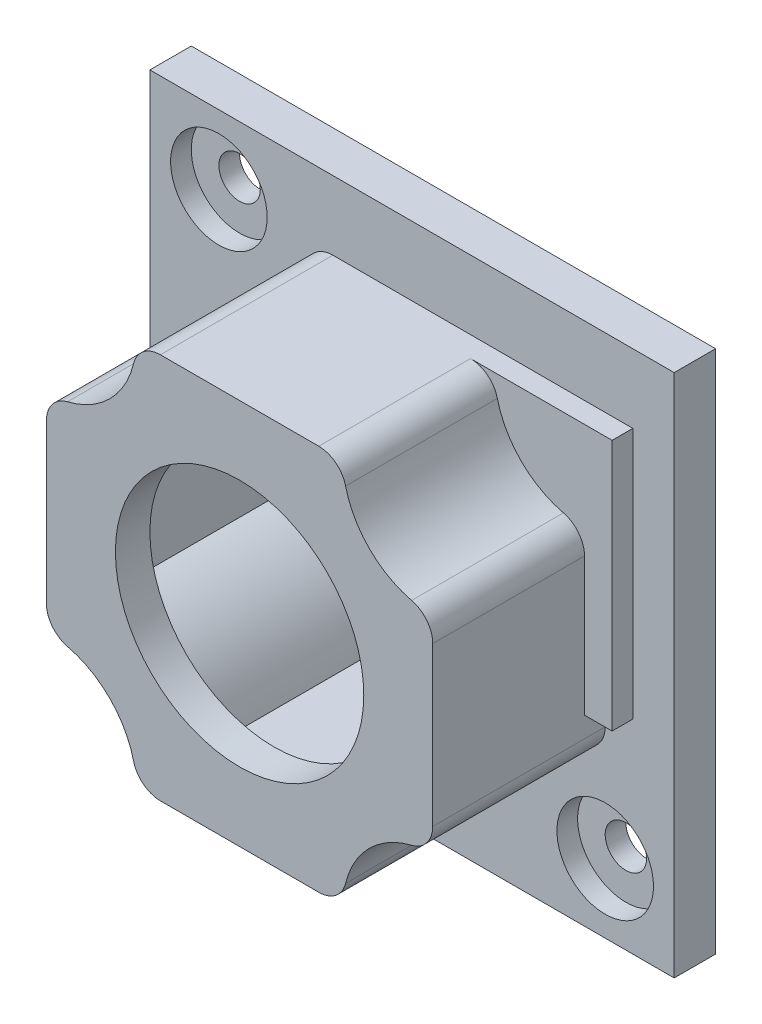
SolidWorks part; units mm, degrees
ref_plane "Front Plane" through (0, 0, 0) normal (1, 0, 0) x (0, 1, 0)
ref_plane "Top Plane" through (0, 0, 0) normal (0, 0, 1) x (0, 1, 0)
ref_plane "Right Plane" through (0, 0, 0) normal (0, 1, 0) x (-1, 0, 0)
sketch "Sketch1" plane through (0, 0, 0) normal (0, 0, 1) x (0, 1, 0)
  line L1 (-19, -19) -> (19, -19)
  line L2 (-19, -19) -> (-19, 19)
  line L3 (-19, 19) -> (19, 19)
  line L4 (19, -19) -> (19, 19)
  line L5 (-19, -19) -> (19, 19) construction
  line L6 (-19, 19) -> (19, -19) construction
  point P0 (0, 0)
  dimension "D1" = 38
extrude "Boss-Extrude1" add sketch "Sketch1" along normal blind 3
sketch "Sketch2" plane through (0, 0, 0) normal (0, 0, -1) x (1, 0, 0)
  line L0 (0, 19) -> (0, -19) construction
  line L1 (-19, 19) -> (19, 19) construction
  line L2 (19, -19) -> (-19, -19) construction
  line L3 (-19, 0) -> (19, 0) construction
  line L4 (-19, -19) -> (-19, 19) construction
  line L5 (19, 19) -> (19, -19) construction
  line L6 (0, 14) -> (-19, 14) construction
  circle A0 centre (-14, 14) radius 1.5
  circle A1 centre (-14, -14) radius 1.5
  circle A2 centre (14, -14) radius 1.5 construction
  circle A3 centre (14, 14) radius 1.5
  dimension "D2" = 3
  dimension "D1" = 14
  dimension "D3" = 14
extrude "Cut-Extrude1" cut sketch "Sketch2" against normal through all
sketch "Sketch3" plane through (0, 0, 3) normal (0, 0, 1) x (1, 0, 0)
  line L0 (-14, 7.5) -> (-14, -7.5)
  line L1 (-7.5, -14) -> (7.5, -14)
  line L2 (14, -7.5) -> (14, 7.5)
  line L3 (-7.5, 14) -> (7.5, 14)
  arc A0 (-14, -7.5) -> (-7.5, -14) centre (-14, -14) cw
  arc A1 (7.5, -14) -> (14, -7.5) centre (14, -14) cw
  arc A2 (-14, 7.5) -> (-7.5, 14) centre (-14, 14) ccw
  arc A3 (7.5, 14) -> (14, 7.5) centre (14, 14) ccw
  circle A4 centre (-14, 14) radius 1.5 construction
  circle A6 centre (14, -14) radius 1.5 construction
  circle A7 centre (-14, -14) radius 1.5 construction
  dimension "D1" = 5
  dimension "D2" = 28
extrude "Boss-Extrude2" add sketch "Sketch3" along normal blind 12.5
sketch "Sketch4" plane through (0, 0, 15.5) normal (0, 0, 1) x (1, 0, 0)
  circle A0 centre (0, 0) radius 9
  dimension "D1" = 18
extrude "Cut-Extrude2" cut sketch "Sketch4" against normal through all
sketch "Sketch5" plane through (0, 0, 15.5) normal (0, 0, 1) x (1, 0, 0)
  line L0 (-11.5, -4.8348) -> (-11.5, 4.8348)
  line L1 (-4.8348, 11.5) -> (4.8348, 11.5)
  line L2 (11.5, 4.8348) -> (11.5, -4.8348)
  line L3 (4.8348, -11.5) -> (-4.8348, -11.5)
  line L4 (7.5, 14) -> (-7.5, 14) construction
  line L5 (-14, 7.5) -> (-14, -7.5) construction
  line L6 (-7.5, -14) -> (7.5, -14) construction
  line L7 (14, -7.5) -> (14, 7.5) construction
  arc A0 (-11.5, 4.8348) -> (-4.8348, 11.5) centre (-14, 14) ccw
  arc A1 (4.8348, 11.5) -> (11.5, 4.8348) centre (14, 14) ccw
  arc A2 (11.5, -4.8348) -> (4.8348, -11.5) centre (14, -14) ccw
  arc A3 (-4.8348, -11.5) -> (-11.5, -4.8348) centre (-14, -14) ccw
  circle A4 centre (-14, -14) radius 1.5 construction
  circle A5 centre (-14, 14) radius 1.5 construction
  circle A7 centre (14, -14) radius 1.5 construction
  arc A8 (-14, 7.5) -> (-7.5, 14) centre (-14, 14) ccw construction
  dimension "D5" = 3
  dimension "D1" = 2.5
  dimension "D2" = 2.5
  dimension "D3" = 2.5
  dimension "D4" = 2.5
extrude "Cut-Extrude3" cut sketch "Sketch5" against normal through all from offset 2.5 offset against normal yes
fillet "Fillet1" radius 2 8 edges at (-14, -7.5, 9.25) (-7.5, -14, 9.25) (7.5, -14, 9.25) (14, -7.5, 9.25) (14, 7.5, 9.25) (7.5, 14, 9.25) (-7.5, 14, 9.25) (-14, 7.5, 9.25)
sketch "Sketch6" plane through (0, 0, 0) normal (0, 0, -1) x (1, 0, 0)
  line L0 (-14, -14) -> (14, -14) construction
  line L1 (14, -14) -> (14, 14) construction
  line L3 (14.5, -12.25) -> (6.5, -12.25)
  line L4 (14.5, -12.25) -> (14.5, 2.75)
  line L5 (14.5, 2.75) -> (6.5, 2.75)
  line L6 (6.5, -12.25) -> (6.5, 2.75)
  circle A0 centre (14, -14) radius 1.5 construction
  circle A1 centre (14, 14) radius 1.5 construction
  dimension "D1" = 1.75
  dimension "D2" = 0.5
  dimension "D3" = 8
  dimension "D4" = 15
extrude "Cut-Extrude4" cut sketch "Sketch6" against normal blind 2.5
sketch "Sketch7" plane through (0, 0, 3) normal (0, 0, 1) x (1, 0, 0)
  line L1 (16, 14) -> (5.7386, 14)
  line L2 (16, 14) -> (16, -4.25)
  line L3 (16, -4.25) -> (14, -4.25)
  line L7 (14.5, 12.25) -> (14.5, -2.75) construction
  line L10 (14.5, -2.75) -> (14, -2.75) construction
  line L11 (14, -4.25) -> (14, 5.7386)
  line L12 (5.7386, 14) -> (-5.7386, 14) construction
  arc A0 (14, 5.7386) -> (12.4706, 7.6825) centre (12, 5.7386) ccw
  arc A1 (12.4706, 7.6825) -> (7.6825, 12.4706) centre (14, 14) cw
  arc A2 (7.6825, 12.4706) -> (12.4706, 7.6825) centre (14, 14) ccw construction
  arc A3 (14, 5.7386) -> (12.4706, 7.6825) centre (12, 5.7386) ccw construction
  arc A4 (7.6825, 12.4706) -> (12.4706, 7.6825) centre (14, 14) ccw construction
  arc A5 (7.6825, 12.4706) -> (5.7386, 14) centre (5.7386, 12) ccw
  arc A6 (7.6825, 12.4706) -> (5.7386, 14) centre (5.7386, 12) ccw construction
  point P12 (0, 0)
  dimension "D2" = 1.5
  dimension "D4" = 1.5
extrude "Boss-Extrude3" add sketch "Sketch7" along normal blind 1.5
sketch "Sketch8" plane through (0, 0, 3) normal (0, 0, 1) x (1, 0, 0)
  circle A0 centre (-14, 14) radius 3.5
  circle A1 centre (-14, -14) radius 3.5
  circle A2 centre (14, -14) radius 3.5
  circle A3 centre (14, -14) radius 1.5 construction
  point P8 (14.3867, -10.4919)
  dimension "D1" = 7
extrude "Cut-Extrude5" cut sketch "Sketch8" against normal blind 1.5
